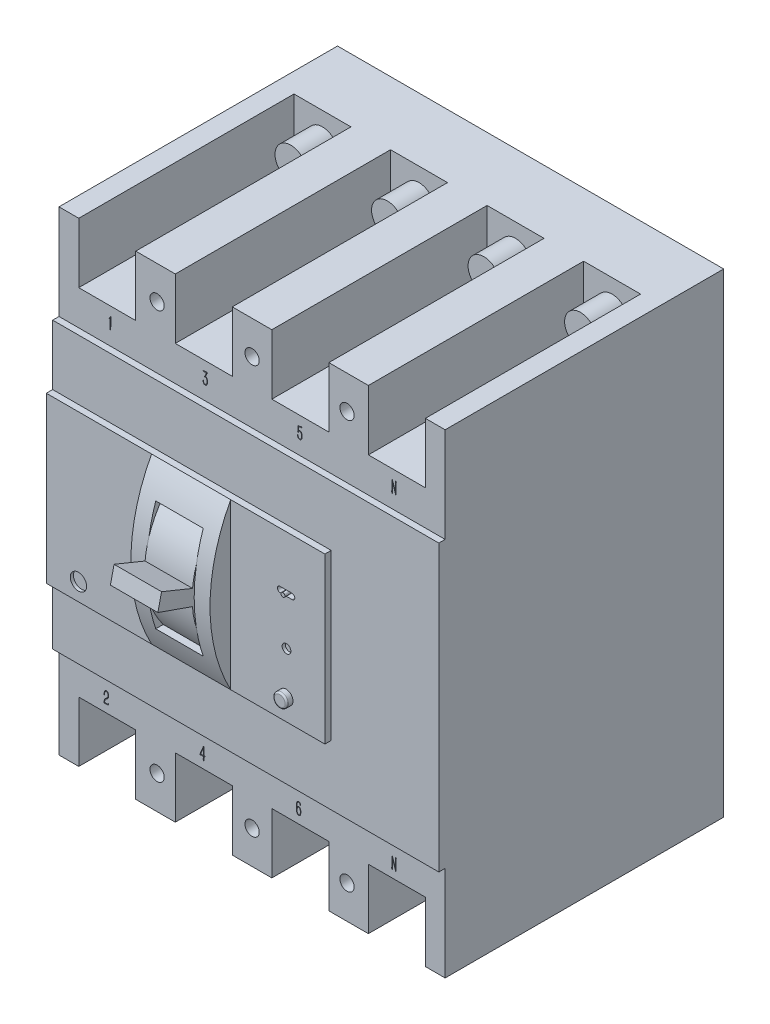
SolidWorks part; units mm, degrees
ref_plane "前视基准面" through (0, 0, 0) normal (0, 0, 1) x (1, 0, 0)
ref_plane "上视基准面" through (0, 0, 0) normal (0, 1, 0) x (1, 0, 0)
ref_plane "右视基准面" through (0, 0, 0) normal (1, 0, 0) x (0, 0, -1)
sketch "草图1" plane through (0, 0, 0) normal (0, 0, 1) x (1, 0, 0)
  line L1 (-61, -75) -> (61, -75)
  line L2 (-61, -75) -> (-61, 75)
  line L3 (-61, 75) -> (61, 75)
  line L4 (61, -75) -> (61, 75)
  line L5 (-61, -75) -> (61, 75) construction
  line L6 (-61, 75) -> (61, -75) construction
  point P0 (0, 0)
  dimension "D1" = 150
  dimension "D2" = 122
extrude "凸台-拉伸1" add sketch "草图1" along normal blind 90
sketch "草图3" plane through (0, 0, 90) normal (0, 0, 1) x (1, 0, 0)
  line L0 (61, -75) -> (61, 75) construction
  line L1 (-61, 75) -> (61, 75)
  line L2 (-61, 75) -> (-61, 45)
  line L3 (-61, 45) -> (61, 45)
  line L4 (61, 75) -> (61, 45)
  line L5 (-61, 75) -> (-61, -75) construction
  line L6 (61, -75) -> (-61, -75)
  line L7 (61, -75) -> (61, -45)
  line L8 (61, -45) -> (-61, -45)
  line L9 (-61, -75) -> (-61, -45)
  dimension "D1" = 30
  dimension "D2" = 30
extrude "切除-拉伸1" cut sketch "草图3" against normal blind 2
sketch "草图4" plane through (0, 0, 90) normal (0, 0, 1) x (1, 0, 0)
  line L1 (-61, 45) -> (-61, -45) construction
  line L2 (27, -26) -> (-61, -26)
  line L3 (27, -26) -> (27, 26)
  line L4 (27, 26) -> (-61, 26)
  line L5 (-61, -26) -> (-61, 26)
  line L6 (27, -26) -> (-61, 26) construction
  line L7 (27, 26) -> (-61, -26) construction
  point P0 (-17, 0)
  dimension "D1" = 52
  dimension "D2" = 88
extrude "凸台-拉伸2" add sketch "草图4" along normal blind 2
sketch "草图5" plane through (0, 0, 88) normal (0, 0, 1) x (1, 0, 0)
  line L0 (0, 45) -> (0, 75) construction
  line L3 (-61, 45) -> (61, 45) construction
  line L4 (61, 75) -> (-61, 75) construction
  line L5 (61, 45) -> (61, 75) construction
  line L6 (36.75, 56) -> (54.75, 56)
  line L7 (36.75, 56) -> (36.75, 75)
  line L8 (36.75, 75) -> (54.75, 75)
  line L9 (54.75, 56) -> (54.75, 75)
  line L10 (36.75, 56) -> (54.75, 75) construction
  line L11 (36.75, 75) -> (54.75, 56) construction
  line L12 (6.25, 56) -> (24.25, 56)
  line L13 (6.25, 56) -> (6.25, 75)
  line L14 (6.25, 75) -> (24.25, 75)
  line L15 (24.25, 56) -> (24.25, 75)
  line L16 (6.25, 56) -> (24.25, 75) construction
  line L17 (6.25, 75) -> (24.25, 56) construction
  line L18 (-6.25, 75) -> (-24.25, 56) construction
  line L19 (-6.25, 56) -> (-24.25, 75) construction
  line L20 (-36.75, 75) -> (-54.75, 56) construction
  line L21 (-36.75, 56) -> (-54.75, 75) construction
  line L22 (-24.25, 56) -> (-24.25, 75)
  line L23 (-6.25, 75) -> (-24.25, 75)
  line L24 (-6.25, 56) -> (-6.25, 75)
  line L25 (-6.25, 56) -> (-24.25, 56)
  line L26 (-54.75, 56) -> (-54.75, 75)
  line L27 (-36.75, 75) -> (-54.75, 75)
  line L28 (-36.75, 56) -> (-36.75, 75)
  line L29 (-36.75, 56) -> (-54.75, 56)
  point P6 (45.75, 65.5)
  point P11 (15.25, 65.5)
  point P26 (-15.25, 65.5)
  point P27 (-45.75, 65.5)
  dimension "D1" = 18
  dimension "D2" = 19
  dimension "D3" = 6.25
  dimension "D4" = 12.5
extrude "切除-拉伸2" cut sketch "草图5" against normal offset from surface (68 mm away) 20 up to face at (0, 0, 0)
sketch "草图27" plane through (0, 0, 20) normal (0, 0, 1) x (1, 0, 0)
  line L0 (36.75, 56) -> (54.75, 56) construction
  line L1 (6.25, 56) -> (24.25, 56) construction
  line L2 (-24.25, 56) -> (-6.25, 56) construction
  line L3 (-54.75, 56) -> (-36.75, 56) construction
  line L4 (-54.75, 75) -> (-54.75, 56) construction
  circle A0 centre (45.75, 65.5) radius 5
  circle A1 centre (15.25, 65.5) radius 5
  circle A2 centre (-15.25, 65.5) radius 5
  circle A3 centre (-45.75, 65.5) radius 5
  point P10 (45.75, 56)
  point P13 (15.25, 56)
  point P16 (-15.25, 56)
  point P19 (-45.75, 56)
  point P22 (-54.75, 65.5)
  dimension "D1" = 10
extrude "凸台-拉伸13" add sketch "草图27" along normal blind 10
mirror "镜向1" about plane through (0, 0, 0) normal (0, 1, 0) of "切除-拉伸2", "凸台-拉伸13"
ref_plane "基准面1" through (-15.25, 0, 0) normal (1, 0, 0) x (0, 0, -1)
sketch "草图22" plane through (-15.25, 0, 0) normal (1, 0, 0) x (0, 0, -1)
  line L0 (-92, -26) -> (-92, 26) construction
  line L1 (-92, 26) -> (-92, -26)
  arc A0 (-92, 26) -> (-92, -26) centre (-43.5335, 0) ccw
  dimension "D1" = 55
extrude "凸台-拉伸10" add sketch "草图22" along normal mid plane 25
sketch "草图24" plane through (0, 0, 92) normal (0, 0, 1) x (1, 0, 0)
  line L0 (-15.25, -54.1934) -> (-15.25, 54.1934) construction
  line L1 (-22.75, -17.5) -> (-7.75, -17.5)
  line L2 (-22.75, -17.5) -> (-22.75, 17.5)
  line L3 (-22.75, 17.5) -> (-7.75, 17.5)
  line L4 (-7.75, -17.5) -> (-7.75, 17.5)
  line L5 (-22.75, -17.5) -> (-7.75, 17.5) construction
  line L6 (-22.75, 17.5) -> (-7.75, -17.5) construction
  point P0 (-15.25, 0)
  dimension "D1" = 15
  dimension "D2" = 35
extrude "切除-拉伸4" cut sketch "草图24" against normal mid plane 15
sketch "草图25" plane through (-22.75, 0, 0) normal (1, 0, 0) x (0, 0, -1)
  circle A0 centre (-70.1762, 0) radius 29
  dimension "D1" = 58
extrude "凸台-拉伸11" add sketch "草图25" along normal up to surface (15 mm away) up to face at (-7.75, 0, 90.8022)
sketch "草图11" plane through (0, 0, 0) normal (0, 0, -1) x (-1, 0, 0)
  line L0 (-42.4591, 0) -> (39.5939, 0) construction
  circle A0 centre (30, 64.5) radius 2.25
  circle A1 centre (0, 64.5) radius 2.25
  circle A2 centre (-30, 64.5) radius 2.25
  circle A3 centre (-30, -64.5) radius 2.25
  circle A4 centre (0, -64.5) radius 2.25
  circle A5 centre (30, -64.5) radius 2.25
  dimension "D1" = 4.5
  dimension "D2" = 30
  dimension "D3" = 30
  dimension "D4" = 129
extrude "切除-拉伸5" cut sketch "草图11" against normal through all
sketch "草图12" plane through (0, 0, 88) normal (0, 0, 1) x (1, 0, 0)
  line L0 (-45.75, 49) -> (45.75, 49) construction
  line L1 (-47.0275, -54) -> (45.75, -54) construction
  line L2 (-61, 45) -> (61, 45) construction
  line L3 (-54.75, 56) -> (-36.75, 56) construction
  line L4 (36.75, 56) -> (54.75, 56) construction
  line L5 (61, -45) -> (-61, -45) construction
  text T0 "135N" font "汉仪长仿宋体" height in points 16
  text T1 "246N" font "汉仪长仿宋体" height in points 16
  point P9 (-45.75, 56)
  point P12 (45.75, 56)
  dimension "D1" = 4
  dimension "D2" = 9
extrude "切除-拉伸6" cut sketch "草图12" against normal blind 1
sketch "草图14" plane through (0, 0, 92) normal (0, 0, 1) x (1, 0, 0)
  circle A0 centre (-50.8512, -20.4916) radius 2.5792
extrude "切除-拉伸7" cut sketch "草图14" against normal blind 1
sketch "草图28" plane through (0, 0, 92) normal (0, 0, 1) x (1, 0, 0)
  circle A0 centre (14.7617, -19.2693) radius 2.1806
extrude "凸台-拉伸14" add sketch "草图28" along normal blind 2
fillet "圆角1" radius 0.5 1 edges at (16.9423, -19.2693, 94)
sketch "草图29" plane through (0, 0, 92) normal (0, 0, 1) x (1, 0, 0)
  circle A0 centre (14.882, -5.9652) radius 1.3791
extrude "切除-拉伸8" cut sketch "草图29" against normal blind 1
sketch "草图30" plane through (0, 0, 92) normal (0, 0, 1) x (1, 0, 0)
  line L0 (12.8665, 9.2192) -> (16.6514, 9.2192) construction
  line L1 (12.8665, 10.0761) -> (16.6514, 10.0761)
  line L2 (12.8665, 8.3622) -> (16.6514, 8.3622)
  arc A0 (12.8665, 10.0761) -> (12.8665, 8.3622) centre (12.8665, 9.2192) ccw
  arc A1 (16.6514, 8.3622) -> (16.6514, 10.0761) centre (16.6514, 9.2192) ccw
  point P2 (14.7589, 9.2192)
extrude "切除-拉伸9" cut sketch "草图30" against normal blind 2
sketch "草图31" plane through (0, 0, 90) normal (0, 0, 1) x (1, 0, 0)
  circle A0 centre (14.7782, 9.2016) radius 0.6209
extrude "凸台-拉伸15" add sketch "草图31" along normal blind 3
sketch "草图32" plane through (0, 0, 20) normal (0, 0, 1) x (1, 0, 0)
  point P0 (-45.75, 65.5)
  point P1 (-15.25, 65.5)
  point P3 (15.25, 65.5)
  point P5 (45.75, 65.5)
  point P7 (45.75, -65.5)
  point P9 (15.25, -65.5)
  point P11 (-15.25, -65.5)
  point P13 (-45.75, -65.5)
sketch "草图33" plane through (-22.75, 0, 0) normal (-1, 0, 0) x (0, 0, 1)
  line L0 (99.0464, 2.7408) -> (108.847, 6.7414)
  line L1 (108.847, 6.7414) -> (110, 1.6118)
  line L2 (110, 1.6118) -> (99.0912, -2.2188)
  line L3 (99.0912, -2.2188) -> (99.0464, -2.2346)
  line L4 (99.0464, -2.2346) -> (99.0464, 2.7408)
  line L5 (0, 75) -> (0, -75) construction
  arc A1 (97.8417, -8.696) -> (97.8417, 8.696) centre (70.1762, 0) ccw construction
  dimension "D1" = 110
extrude "凸台-拉伸16" add sketch "草图33" against normal blind 15
sketch "0_0_Point" plane through (0, 0, 20) normal (0, 0, 1) x (1, 0, 0)
  point P0 (-45.75, 65.5)
other "0_0" parameters "直径"=2, "端头长度"=2
ref_axis "基准轴1" through (-45.75, 65.5, 30) along (0, 0, -1)
sketch "0_1_Point" plane through (0, 0, 20) normal (0, 0, 1) x (1, 0, 0)
  point P0 (-45.75, -65.5)
other "0_1" parameters "直径"=2, "端头长度"=2
ref_axis "基准轴2" through (-45.75, -65.5, 30) along (0, 0, -1)
sketch "1_0_Point" plane through (0, 0, 20) normal (0, 0, 1) x (1, 0, 0)
  point P0 (-15.25, 65.5)
other "1_0" parameters "直径"=2, "端头长度"=2
ref_axis "基准轴3" through (-15.25, 65.5, 30) along (0, 0, -1)
sketch "1_1_Point" plane through (0, 0, 20) normal (0, 0, 1) x (1, 0, 0)
  point P0 (-15.25, -65.5)
other "1_1" parameters "直径"=2, "端头长度"=2
ref_axis "基准轴4" through (-15.25, -65.5, 30) along (0, 0, -1)
sketch "2_0_Point" plane through (0, 0, 20) normal (0, 0, 1) x (1, 0, 0)
  point P0 (15.25, 65.5)
other "2_0" parameters "直径"=2, "端头长度"=2
ref_axis "基准轴5" through (15.25, 65.5, 30) along (0, 0, -1)
sketch "2_1_Point" plane through (0, 0, 20) normal (0, 0, 1) x (1, 0, 0)
  point P0 (15.25, -65.5)
other "2_1" parameters "直径"=2, "端头长度"=2
ref_axis "基准轴6" through (15.25, -65.5, 30) along (0, 0, -1)
sketch "3_0_Point" plane through (0, 0, 20) normal (0, 0, 1) x (1, 0, 0)
  point P0 (45.75, 65.5)
other "3_0" parameters "直径"=2, "端头长度"=2
ref_axis "基准轴7" through (45.75, 65.5, 30) along (0, 0, -1)
sketch "3_1_Point" plane through (0, 0, 20) normal (0, 0, 1) x (1, 0, 0)
  point P0 (45.75, -65.5)
other "3_1" parameters "直径"=2, "端头长度"=2
ref_axis "基准轴8" through (45.75, -65.5, 30) along (0, 0, -1)
